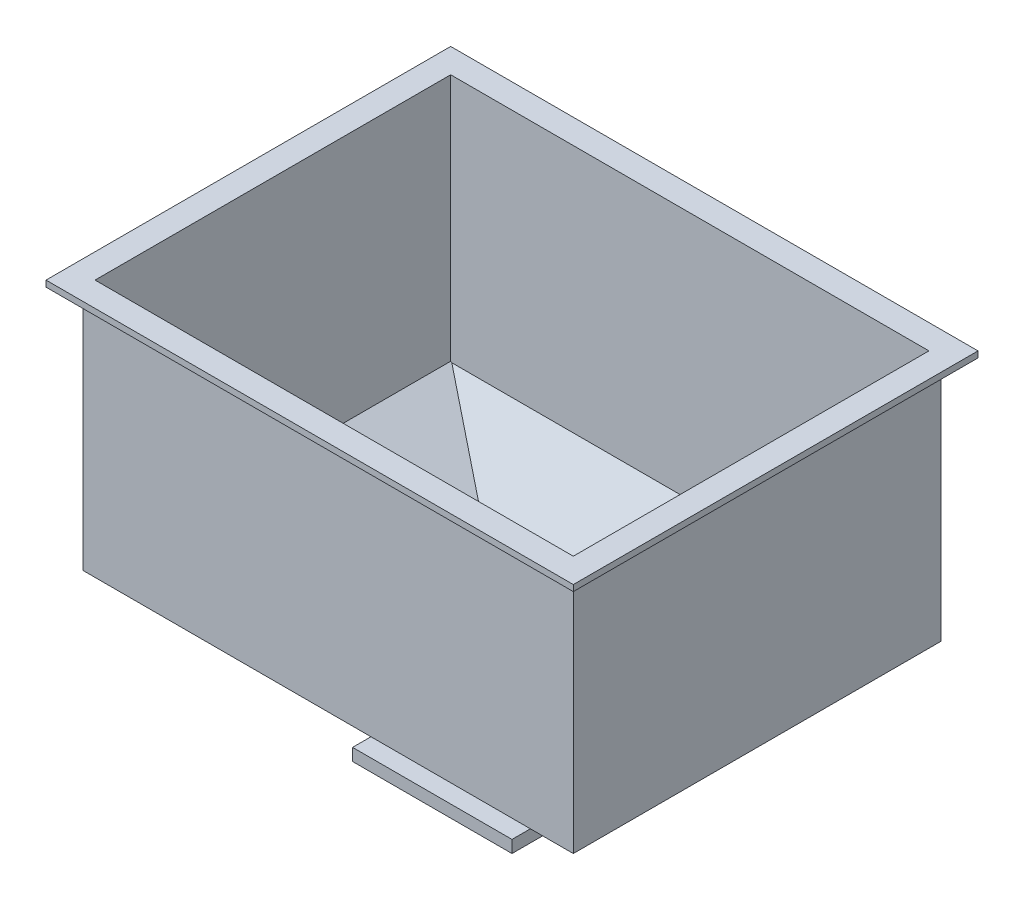
SolidWorks part; units mm, degrees
ref_plane "Front Plane" through (0, 0, 0) normal (0, 0, 1) x (1, 0, 0)
ref_plane "Top Plane" through (0, 0, 0) normal (0, 1, 0) x (1, 0, 0)
ref_plane "Right Plane" through (0, 0, 0) normal (1, 0, 0) x (0, 0, -1)
sketch "Sketch1" plane through (0, 0, 0) normal (0, 0, 1) x (1, 0, 0)
  line L0 (-200, -100) -> (-50, -200)
  line L1 (-200, 100) -> (200, 100)
  line L2 (-200, 100) -> (-200, -100)
  line L3 (-200, -100) -> (200, -100)
  line L4 (200, 100) -> (200, -100)
  line L5 (-50, -200) -> (50, -200)
  line L6 (50, -200) -> (200, -100)
  point P6 (0, -200)
  point P7 (0, -100)
  point P14 (200, 0)
  point P15 (0, 100)
  dimension "D1" = 200
  dimension "D2" = 400
  dimension "D3" = 100
  dimension "D4" = 100
extrude "Boss-Extrude1" add sketch "Sketch1" against normal blind 300 contours L4 L1 L2 L3 | L5 L6 L3 L0 region at (0, -140, 0) region at (0, 0, 0)
sketch "Sketch2" plane through (0, 0, 0) normal (1, 0, 0) x (0, 0, -1)
  line L0 (0, -100) -> (100, -200)
  line L1 (300, -200) -> (0, -200) construction
  line L2 (100, -200) -> (0, -200)
  line L3 (0, -200) -> (0, -100)
  line L4 (300, -100) -> (300, -200)
  line L5 (300, -200) -> (300, -100) construction
  line L6 (300, -200) -> (200, -200)
  line L7 (200, -200) -> (300, -100)
  dimension "D1" = 100
  dimension "D2" = 100
  dimension "D3" = 100
extrude "Cut-Extrude1" cut sketch "Sketch2" against normal through all both and the other way through all
shell "Shell1" thickness 5 removed face at (0, -200, -150) removed face at (0, 100, -150)
ref_plane "Plane1" through (0, 100, 0) normal (0, 1, 0) x (1, 0, 0)
sketch "Sketch3" plane through (0, 100, 0) normal (0, 1, 0) x (1, 0, 0)
  line L0 (-200, 0) -> (200, 0) construction
  line L1 (-215, 315) -> (215, 315)
  line L2 (-215, 315) -> (-215, -15)
  line L3 (-215, -15) -> (215, -15)
  line L4 (215, 315) -> (215, -15)
  line L5 (200, 300) -> (200, 0) construction
  point P6 (0, 0)
  point P7 (0, -15)
  point P8 (215, 150)
  point P11 (200, 150)
  dimension "D1" = 330
  dimension "D2" = 430
extrude "Boss-Extrude2" add sketch "Sketch3" along normal blind 5
shell "Shell2" thickness 5 removed face at (0, 100, -150) removed face at (0, 105, -150)
ref_plane "Plane5" through (0, -200, 0) normal (0, -1, 0) x (-1, 0, 0)
sketch "Sketch5" plane through (0, -200, 0) normal (0, -1, 0) x (1, 0, 0)
  line L0 (-50, -200) -> (-50, -100) construction
  line L1 (65, -215) -> (-65, -215)
  line L2 (65, -215) -> (65, -85)
  line L3 (65, -85) -> (-65, -85)
  line L4 (-65, -215) -> (-65, -85)
  line L8 (-50, -200) -> (50, -200) construction
  point P4 (-50, -150)
  point P7 (-65, -150)
  point P10 (0, -215)
  point P13 (0, -200)
  dimension "D1" = 130
  dimension "D2" = 130
extrude "Boss-Extrude3" add sketch "Sketch5" along normal blind 10
sketch "Sketch6" plane through (0, -210, 0) normal (0, -1, 0) x (1, 0, 0)
  line L0 (65, -85) -> (-65, -85) construction
  line L1 (-65, -85) -> (-65, -215) construction
  circle A0 centre (0, -150) radius 9
  circle A1 centre (0, -150) radius 12
  point P2 (0, 0)
  point P5 (0, -85)
  point P8 (-65, -150)
  dimension "D1" = 18
  dimension "D2" = 3
extrude "Boss-Extrude4" [suppressed] add sketch "Sketch6" along normal blind 30
